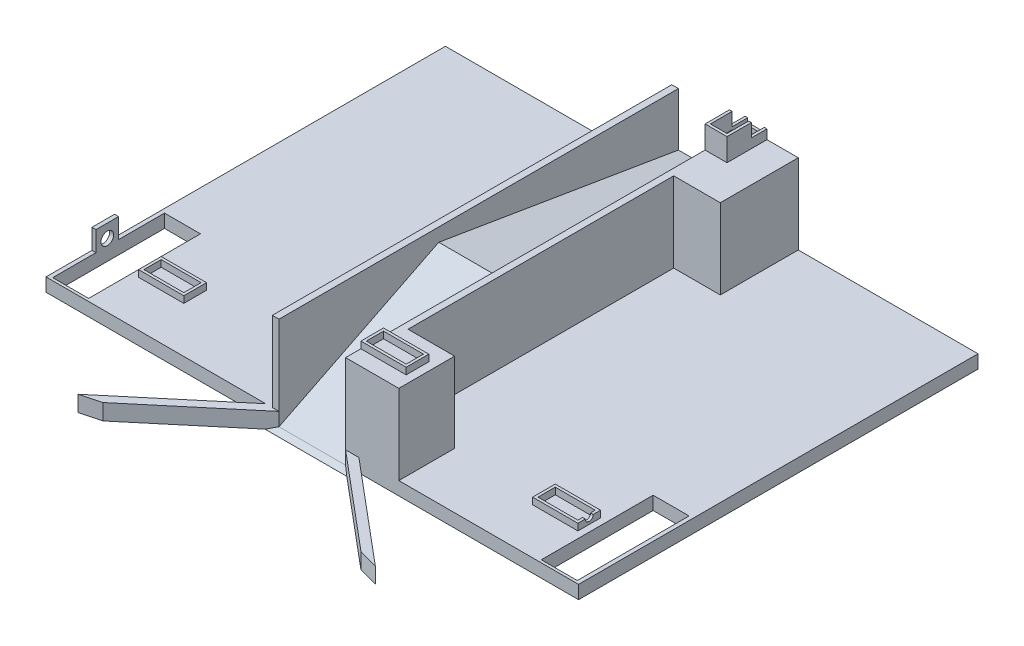
SolidWorks part; units mm, degrees
ref_plane "Front Plane" through (0, 0, 0) normal (0, 0, 1) x (1, 0, 0)
ref_plane "Top Plane" through (0, 0, 0) normal (0, 1, 0) x (1, 0, 0)
ref_plane "Right Plane" through (0, 0, 0) normal (1, 0, 0) x (0, 0, -1)
sketch "Sketch1" plane through (0, 0, 0) normal (0, 1, 0) x (1, 0, 0)
  line L1 (-117.9466, 258.1119) -> (282.0534, 258.1119)
  line L2 (-117.9466, 258.1119) -> (-117.9466, 44.1119)
  line L3 (-87.9466, -41.8881) -> (252.0534, -41.8881)
  line L5 (-117.9466, 44.1119) -> (-87.9466, 44.1119)
  line L8 (-87.9466, 44.1119) -> (-87.9466, -41.8881)
  line L23 (82.0534, 258.1119) -> (82.0534, -41.8881) construction
  line L32 (282.0534, 44.1119) -> (252.0534, 44.1119)
  line L33 (282.0534, 258.1119) -> (282.0534, 44.1119)
  line L34 (252.0534, 44.1119) -> (252.0534, -41.8881)
  point P32 (199.0884, -22.3492)
  dimension "D3" = 200
  dimension "D4" = 300
  dimension "D2" = 86
  dimension "D11" = 30
  dimension "D5" = 170
extrude "Boss-Extrude3" add sketch "Sketch1" along normal blind 10
sketch "Sketch2" plane through (0, 10, 0) normal (0, 1, 0) x (1, 0, 0)
  line L1 (-82.9466, 9.6119) -> (-48.9466, 9.6119)
  line L2 (-87.9466, 44.1119) -> (-87.9466, -41.8881) construction
  line L3 (-82.9466, 9.6119) -> (-82.9466, -7.3881)
  line L4 (-82.9466, -7.3881) -> (-48.9466, -7.3881)
  line L5 (-48.9466, 9.6119) -> (-48.9466, -7.3881)
  line L7 (-80.9466, 7.6119) -> (-50.9466, 7.6119)
  line L8 (-80.9466, 7.6119) -> (-80.9466, -5.3881)
  line L9 (-80.9466, -5.3881) -> (-50.9466, -5.3881)
  line L10 (-50.9466, 7.6119) -> (-50.9466, -5.3881)
  line L11 (-48.9466, 1.1119) -> (-82.9466, 1.1119) construction
  line L12 (-87.9466, -41.8881) -> (252.0534, -41.8881) construction
  line L13 (82.0534, 258.1119) -> (82.0534, -41.8881) construction
  line L14 (282.0534, 258.1119) -> (-117.9466, 258.1119) construction
  line L15 (213.0534, 1.1119) -> (247.0534, 1.1119) construction
  line L17 (215.0534, 7.6119) -> (215.0534, -5.3881)
  line L18 (245.0534, -5.3881) -> (215.0534, -5.3881)
  line L19 (245.0534, 7.6119) -> (245.0534, -5.3881)
  line L20 (245.0534, 7.6119) -> (215.0534, 7.6119)
  line L21 (213.0534, 9.6119) -> (213.0534, -7.3881)
  line L22 (247.0534, -7.3881) -> (213.0534, -7.3881)
  line L23 (247.0534, 9.6119) -> (247.0534, -7.3881)
  line L24 (247.0534, 9.6119) -> (213.0534, 9.6119)
  dimension "D1" = 2
  dimension "D3" = 2
  dimension "D4" = 2
  dimension "D5" = 30
  dimension "D6" = 13
  dimension "D7" = 43
  dimension "D2" = 2
  dimension "D8" = 5
extrude "Boss-Extrude4" add sketch "Sketch2" along normal blind 5
sketch "Sketch3" plane through (0, 10, 0) normal (0, 1, 0) x (1, 0, 0)
  line L0 (82.0534, 258.1119) -> (82.0534, -41.8881) construction
  line L1 (282.0534, 258.1119) -> (-117.9466, 258.1119) construction
  line L2 (-87.9466, -41.8881) -> (252.0534, -41.8881) construction
  line L3 (57.0534, -41.8881) -> (57.0534, 78.1119)
  line L4 (57.0534, 78.1119) -> (107.0534, 78.1119)
  line L5 (107.0534, 78.1119) -> (107.0534, -41.8881)
  line L24 (252.0534, -41.8881) -> (252.0534, 44.1119)
  line L25 (252.0534, 44.1119) -> (282.0534, 44.1119)
  line L26 (282.0534, 44.1119) -> (282.0534, 258.1119)
  line L27 (282.0534, 258.1119) -> (-117.9466, 258.1119)
  line L28 (-117.9466, 258.1119) -> (-117.9466, 44.1119)
  line L29 (-117.9466, 44.1119) -> (-87.9466, 44.1119)
  line L30 (-87.9466, 44.1119) -> (-87.9466, -41.8881)
  line L35 (-87.9466, -41.8881) -> (252.0534, -41.8881)
  line L51 (57.0534, -41.8881) -> (107.0534, -41.8881)
  dimension "D1" = 50
  dimension "D2" = 25
  dimension "D3" = 120
extrude "Boss-Extrude5" add sketch "Sketch3" along normal blind 50
sketch "Sketch4" plane through (107.0534, 0, 0) normal (1, 0, 0) x (0, 0, -1)
  line L2 (-41.8881, 60) -> (78.1119, 60)
  line L3 (78.1119, 60) -> (-41.8881, 0)
  line L4 (-41.8881, 60) -> (-41.8881, 0)
extrude "Cut-Extrude2" cut sketch "Sketch4" against normal up to vertex (50 mm away) up to point (57.0534, 60, 41.8881)
sketch "Sketch5" plane through (0, 10, 0) normal (0, 1, 0) x (1, 0, 0)
  line L0 (57.0534, 78.1119) -> (57.0534, 258.1119)
  line L1 (282.0534, 258.1119) -> (-117.9466, 258.1119) construction
  line L2 (57.0534, 258.1119) -> (107.0534, 258.1119)
  line L3 (107.0534, 258.1119) -> (107.0534, 78.1119)
  line L4 (57.0534, 78.1119) -> (107.0534, 78.1119)
  line L5 (57.0534, 78.1119) -> (57.0534, -21.8881) construction
extrude "Boss-Extrude6" add sketch "Sketch5" along normal blind 50
sketch "Sketch6" plane through (107.0534, 0, 0) normal (1, 0, 0) x (0, 0, -1)
  line L2 (78.1119, 60) -> (258.1119, 60)
  line L3 (258.1119, 60) -> (258.1119, 30)
  line L4 (258.1119, 60) -> (258.1119, 10) construction
  line L5 (258.1119, 30) -> (78.1119, 60)
  dimension "D1" = 30
extrude "Cut-Extrude3" cut sketch "Sketch6" against normal through all contours L2 L3 L5
sketch "Sketch7" plane through (0, 0, 0) normal (0, 1, 0) x (1, 0, 0)
  line L0 (52.0534, 258.1119) -> (52.0534, -41.8881)
  line L1 (57.0534, 258.1119) -> (-117.9466, 258.1119) construction
  line L2 (-87.9466, -41.8881) -> (57.0534, -41.8881) construction
  line L3 (52.0534, -41.8881) -> (57.0534, -41.8881)
  line L4 (57.0534, -41.8881) -> (57.0534, 258.1119)
  line L5 (57.0534, 258.1119) -> (57.0534, -21.8881) construction
  line L6 (57.0534, 258.1119) -> (107.0534, 258.1119) construction
  line L7 (57.0534, 258.1119) -> (52.0534, 258.1119)
  line L8 (107.0534, 258.1119) -> (112.0534, 258.1119)
  line L9 (282.0534, 258.1119) -> (107.0534, 258.1119) construction
  line L10 (112.0534, 258.1119) -> (112.0534, -41.8881)
  line L11 (107.0534, -41.8881) -> (252.0534, -41.8881) construction
  line L12 (112.0534, -41.8881) -> (107.0534, -41.8881)
  line L13 (107.0534, -41.8881) -> (107.0534, 258.1119)
  line L14 (112.0534, -41.8881) -> (147.0534, -41.8881)
  line L15 (107.0534, -41.8881) -> (252.0534, -41.8881) construction
  line L16 (147.0534, -41.8881) -> (147.0534, 0)
  line L17 (147.0534, 0) -> (112.0534, 0)
  dimension "D1" = 5
  dimension "D2" = 5
  dimension "D3" = 35
extrude "Boss-Extrude7" add sketch "Sketch7" along normal blind 70 contours L16 L17 L10 L14 | L7 L0 L3 L4 | L13 L8 L10 L12 region at (129.5534, 0, 20.9441)
sketch "Sketch9" plane through (0, 70, 0) normal (0, 1, 0) x (1, 0, 0)
  line L0 (107.0534, -41.8881) -> (107.0534, 78.1119) construction
  line L1 (107.0534, -13.3881) -> (141.0534, -13.3881)
  line L2 (107.0534, -13.3881) -> (107.0534, -30.3881)
  line L3 (107.0534, -30.3881) -> (141.0534, -30.3881)
  line L4 (141.0534, -13.3881) -> (141.0534, -30.3881)
  line L5 (141.0534, -21.8881) -> (107.0534, -21.8881) construction
  line L6 (109.0534, -15.3881) -> (139.0534, -15.3881)
  line L7 (109.0534, -15.3881) -> (109.0534, -28.3881)
  line L8 (109.0534, -28.3881) -> (139.0534, -28.3881)
  line L9 (139.0534, -15.3881) -> (139.0534, -28.3881)
  line L10 (124.0534, -13.3881) -> (124.0534, -35.4954) construction
  line L11 (147.0534, -41.8881) -> (107.0534, -41.8881) construction
  dimension "D1" = 2
  dimension "D2" = 2
  dimension "D3" = 2
  dimension "D4" = 2
  dimension "D5" = 30
  dimension "D6" = 13
  dimension "D7" = 20
extrude "Boss-Extrude8" add sketch "Sketch9" along normal blind 5 contours L2 L1 L4 L3 | L7 L6 L9 L8
sketch "Sketch10" plane through (112.0534, 0, 0) normal (1, 0, 0) x (0, 0, -1)
  line L0 (199.5615, 70) -> (199.5615, 10)
  line L1 (258.1119, 70) -> (0, 70) construction
  line L2 (0, 10) -> (258.1119, 10) construction
  line L3 (199.5615, 10) -> (258.1119, 10)
  line L4 (258.1119, 10) -> (258.1119, 70)
  line L5 (258.1119, 70) -> (199.5615, 70)
extrude "Boss-Extrude9" add sketch "Sketch10" along normal blind 35
sketch "Sketch13" plane through (0, 70, 0) normal (0, 1, 0) x (1, 0, 0)
  line L0 (123.5534, 228.1119) -> (107.0534, 228.1119)
  line L2 (107.0534, 228.1119) -> (107.0534, 258.1119)
  line L3 (107.0534, 258.1119) -> (123.5534, 258.1119)
  line L4 (123.5534, 258.1119) -> (123.5534, 228.1119)
  line L5 (121.5534, 230.1119) -> (109.0534, 230.1119)
  line L6 (109.0534, 230.1119) -> (109.0534, 256.1119)
  line L7 (109.0534, 256.1119) -> (121.5534, 256.1119)
  line L8 (121.5534, 256.1119) -> (121.5534, 230.1119)
  line L15 (107.0534, 258.1119) -> (147.0534, 258.1119) construction
  dimension "D2" = 16.5
  dimension "D3" = 30
  dimension "D4" = 2
  dimension "D5" = 2
  dimension "D6" = 2
  dimension "D7" = 2
extrude "Boss-Extrude11" add sketch "Sketch13" along normal blind 7
sketch "Sketch14" plane through (0, 0, 0) normal (0, -1, 0) x (1, 0, 0)
  line L0 (282.0534, -44.1119) -> (282.0534, -258.1119) construction
  line L1 (282.0534, -258.1119) -> (-117.9466, -258.1119) construction
  circle A0 centre (267.0534, -243.1119) radius 8
  dimension "D1" = 15
  dimension "D2" = 15
sketch "Sketch16" plane through (0, 0, 0) normal (0, -1, 0) x (1, 0, 0)
  line L0 (-117.9466, -258.1119) -> (-117.9466, -44.1119) construction
  line L1 (282.0534, -258.1119) -> (-117.9466, -258.1119) construction
  circle A0 centre (-102.9466, -243.1119) radius 8
  dimension "D1" = 15
  dimension "D2" = 15
sketch "Sketch19" plane through (0, 0, 41.8881) normal (0, 0, 1) x (1, 0, 0)
  line L0 (-87.9466, 10) -> (52.0534, 10) construction
  line L1 (57.0534, 0) -> (47.0534, 0)
  line L2 (57.0534, 0) -> (57.0534, 10)
  line L3 (57.0534, 10) -> (47.0534, 10)
  line L4 (47.0534, 0) -> (47.0534, 10)
  line L6 (107.0534, 0) -> (117.0534, 0)
  line L7 (107.0534, 0) -> (107.0534, 10)
  line L8 (107.0534, 10) -> (117.0534, 10)
  line L9 (117.0534, 0) -> (117.0534, 10)
  dimension "D1" = 10
  dimension "D2" = 10
  dimension "D3" = 10
sketch "Sketch20" plane through (0, 0, 0) normal (0, 1, 0) x (1, 0, 0)
  line L0 (47.0534, -41.8881) -> (-29.551, -106.1669)
  line L2 (57.0534, -41.8881) -> (-14.8596, -102.2304)
  line L4 (-87.9466, -41.8881) -> (52.0534, -41.8881) construction
  line L5 (107.0534, -41.8881) -> (178.9665, -102.2304)
  line L6 (117.0534, -41.8881) -> (193.6579, -106.1669)
  line L7 (107.0534, -41.8881) -> (117.0534, -41.8881) construction
  line L8 (147.0534, -41.8881) -> (107.0534, -41.8881) construction
  line L9 (178.9665, -102.2304) -> (193.6579, -106.1669)
  line L10 (-14.8596, -102.2304) -> (-29.551, -106.1669)
  line L11 (47.0534, -41.8881) -> (57.0534, -41.8881)
  line L12 (107.0534, -41.8881) -> (117.0534, -41.8881)
  dimension "D1" = 40
  dimension "D2" = 40
  dimension "D3" = 25
  dimension "D4" = 25
  dimension "D5" = 100
  dimension "D6" = 100
  dimension "D7" = 10
  dimension "D8" = 10
extrude "Boss-Extrude16" add sketch "Sketch20" along normal blind 10 and the other way blind 2
sketch "Sketch21" plane through (0, 0, 0) normal (0, -1, 0) x (1, 0, 0)
  line L1 (57.0534, 41.8881) -> (107.0534, 41.8881)
  line L2 (57.0534, 31.8881) -> (57.0534, 11.8881)
  line L3 (57.0534, 11.8881) -> (107.0534, 11.8881)
  line L4 (107.0534, 31.8881) -> (107.0534, 11.8881)
  line L5 (47.0534, 41.8881) -> (47.0534, 31.8881)
  line L6 (47.0534, 31.8881) -> (57.0534, 31.8881)
  line L7 (117.0534, 41.8881) -> (117.0534, 31.8881)
  line L8 (107.0534, 41.8881) -> (117.0534, 41.8881) construction
  line L9 (117.0534, 31.8881) -> (107.0534, 31.8881)
  line L10 (47.0534, 41.8881) -> (57.0534, 41.8881)
  line L11 (107.0534, 41.8881) -> (117.0534, 41.8881)
  dimension "D1" = 50
  dimension "D2" = 30
  dimension "D3" = 10
  dimension "D4" = 10
extrude "Boss-Extrude19" add sketch "Sketch21" along normal blind 2
sketch "Sketch23" plane through (107.0534, 0, 0) normal (1, 0, 0) x (0, 0, -1)
  line L4 (-41.8881, 0) -> (-46.6881, -2)
  line L5 (-102.2304, -2) -> (-41.8881, -2) construction
  line L6 (-46.6881, -2) -> (-41.8881, -2)
  line L7 (-41.8881, -2) -> (-41.8881, 0) construction
  line L8 (-41.8881, 0) -> (-41.8881, -2)
  dimension "D1" = 22.62
extrude "Boss-Extrude23" add sketch "Sketch23" against normal up to surface and the other way up to surface separate body contours L8 L6 L4 up to face at (28.2882, 3.2, 66.025) other way up to face at (135.8187, 3.2, 66.025)
sketch "Sketch28" plane through (0, 0, -44.1119) normal (0, 0, 1) x (1, 0, 0)
  line L0 (-117.9466, 0) -> (-87.9466, 0) construction
  line L1 (-117.9466, 10) -> (-114.9466, 10)
  line L2 (-117.9466, 10) -> (-117.9466, 0)
  line L3 (-117.9466, 0) -> (-114.9466, 0)
  line L4 (-114.9466, 10) -> (-114.9466, 0)
  dimension "D1" = 3
extrude "Boss-Extrude24" add sketch "Sketch28" along normal up to vertex (86 mm away) up to point (-87.9466, 0, 41.8881)
sketch "Sketch30" plane through (0, 0, -44.1119) normal (0, 0, 1) x (1, 0, 0)
  line L0 (252.0534, 0) -> (282.0534, 0) construction
  line L1 (282.0534, 10) -> (279.0534, 10)
  line L2 (282.0534, 10) -> (282.0534, 0)
  line L3 (282.0534, 0) -> (279.0534, 0)
  line L4 (279.0534, 10) -> (279.0534, 0)
  dimension "D1" = 3
extrude "Boss-Extrude26" add sketch "Sketch30" along normal up to vertex (86 mm away) up to point (252.0534, 0, 41.8881)
sketch "Sketch32" plane through (0, 70, 0) normal (0, 1, 0) x (1, 0, 0)
  line L0 (109.0534, 256.1119) -> (109.0534, 230.1119) construction
  line L1 (121.5534, 230.1119) -> (109.0534, 230.1119)
  line L2 (121.5534, 230.1119) -> (121.5534, 246.4119)
  line L3 (121.5534, 246.4119) -> (109.0534, 246.4119)
  line L4 (109.0534, 230.1119) -> (109.0534, 246.4119)
  dimension "D1" = 16.3
extrude "Boss-Extrude28" add sketch "Sketch32" along normal blind 5
sketch "Sketch34" plane through (0, 77, 0) normal (0, 1, 0) x (1, 0, 0)
  line L0 (109.0534, 246.4119) -> (107.0534, 246.4119)
  line L1 (107.0534, 258.1119) -> (107.0534, 228.1119) construction
  line L2 (107.0534, 246.4119) -> (107.0534, 228.1119)
  line L3 (107.0534, 228.1119) -> (123.5534, 228.1119)
  line L4 (107.0534, 228.1119) -> (123.5534, 228.1119) construction
  line L5 (123.5534, 228.1119) -> (123.5534, 246.4119)
  line L6 (123.5534, 228.1119) -> (123.5534, 258.1119) construction
  line L7 (123.5534, 246.4119) -> (121.5534, 246.4119)
  line L8 (121.5534, 246.4119) -> (121.5534, 230.1119)
  line L9 (121.5534, 230.1119) -> (109.0534, 230.1119)
  line L10 (109.0534, 230.1119) -> (109.0534, 246.4119)
extrude "Boss-Extrude31" add sketch "Sketch34" along normal blind 10
sketch "Sketch35" plane through (0, 0, -258.1119) normal (0, 0, -1) x (-1, 0, 0)
  line L0 (-121.5534, 77) -> (-121.5534, 74)
  line L1 (-123.5534, 77) -> (-107.0534, 77) construction
  line L2 (-121.5534, 74) -> (-109.0534, 74)
  line L3 (-109.0534, 74) -> (-109.0534, 77)
  line L4 (-123.5534, 77) -> (-123.5534, 70) construction
  line L5 (-107.0534, 77) -> (-107.0534, 30) construction
  line L6 (-121.5534, 77) -> (-109.0534, 77)
  dimension "D1" = 2
  dimension "D2" = 2
  dimension "D3" = 3
extrude "Cut-Extrude4" cut sketch "Sketch35" against normal up to next (2 mm away)
sketch "Sketch47" plane through (247.0534, 0, 0) normal (1, 0, 0) x (0, 0, -1)
  line L0 (-7.3881, 15) -> (9.6119, 15) construction
  line L1 (-1.8881, 15) -> (4.1119, 15)
  arc A0 (4.1119, 15) -> (-1.8881, 15) centre (1.1119, 15) cw
  dimension "D1" = 3
extrude "Cut-Extrude14" cut sketch "Sketch47" against normal up to next (2 mm away)
sketch "Sketch41" plane through (0, 10, 0) normal (0, 1, 0) x (1, 0, 0)
  line L0 (-117.9466, 9.6119) -> (-114.9466, 9.6119)
  line L1 (-117.9466, -41.8881) -> (-117.9466, 258.1119) construction
  line L2 (-114.9466, -41.8881) -> (-114.9466, 44.1119) construction
  line L3 (-114.9466, 9.6119) -> (-114.9466, -7.3881)
  line L4 (-114.9466, -7.3881) -> (-117.9466, -7.3881)
  line L5 (-117.9466, -7.3881) -> (-117.9466, 9.6119)
  line L6 (-117.9466, 9.6119) -> (-82.9466, 9.6119) construction
  line L7 (-117.9466, -7.3881) -> (-82.9466, -7.3881) construction
extrude "Boss-Extrude33" add sketch "Sketch41" along normal blind 15
sketch "Sketch42" plane through (-117.9466, 0, 0) normal (-1, 0, 0) x (0, 0, 1)
  line L0 (-9.6119, 25) -> (-9.6119, 10) construction
  line L3 (-9.6119, 15) -> (7.3881, 15) construction
  line L4 (7.3881, 25) -> (7.3881, 10) construction
  line L5 (41.8881, 10) -> (-258.1119, 10) construction
  circle A0 centre (-1.1119, 15) radius 4.75
  dimension "D2" = 9.5
  dimension "D1" = 5
extrude "Cut-Extrude11" cut sketch "Sketch42" against normal up to next (3 mm away)
extrude "Boss-Extrude34" add sketch "Sketch14" along normal blind 5
extrude "Boss-Extrude35" add sketch "Sketch16" along normal blind 5
sketch "Sketch43" plane through (-87.9466, 0, 0) normal (-1, 0, 0) x (0, 0, 1)
  line L0 (-44.1119, 0) -> (41.8881, 0) construction
  line L1 (41.8881, 10) -> (39.8881, 10)
  line L2 (41.8881, 10) -> (41.8881, 0)
  line L3 (41.8881, 0) -> (39.8881, 0)
  line L4 (39.8881, 10) -> (39.8881, 0)
  dimension "D1" = 2
extrude "Boss-Extrude36" add sketch "Sketch43" along normal up to next (27 mm away)
sketch "Sketch44" plane through (252.0534, 0, 0) normal (1, 0, 0) x (0, 0, -1)
  line L0 (-41.8881, 0) -> (44.1119, 0) construction
  line L1 (-41.8881, 10) -> (-39.8881, 10)
  line L2 (-41.8881, 10) -> (-41.8881, 0)
  line L3 (-41.8881, 0) -> (-39.8881, 0)
  line L4 (-39.8881, 10) -> (-39.8881, 0)
  dimension "D1" = 2
extrude "Boss-Extrude37" add sketch "Sketch44" along normal up to next
equation "\"draggingScrewDiameter\"= 2"
equation "\"chassisWidth\"= 400"
equation "\"D3@Sketch1\"=0.5 * \"chassisWidth\""
equation "\"chassisLength\"=300"
equation "\"D4@Sketch1\"=\"chassisLength\""
equation "\"wheelDepth\"= 86"
equation "\"D2@Sketch1\"=\"wheelDepth\""
equation "\"wheelWidth\"= 30"
equation "\"baseThickness\"=10"
equation "\"D1@Boss-Extrude3\"=\"baseThickness\""
equation "\"D7@Sketch2\"=\"wheelDepth\" * 0.5"
equation "\"rampLength\"=120"
equation "\"D3@Sketch3\"=\"rampLength\""
equation "\"rampHeight\"=50"
equation "\"D1@Boss-Extrude5\"=\"rampHeight\""
equation "\"D1@Boss-Extrude6\"=\"rampHeight\""
equation "\"dumpHeight\"=30"
equation "\"D1@Sketch6\"=\"dumpHeight\""
equation "\"D11@Sketch1\"=\"wheelWidth\""
equation "\"D5@Sketch1\"=(0.5 * \"chassisWidth\") - \"wheelWidth\""
equation "\"D1@Sketch23\"=atn(\"rampHeight\"/\"rampLength\")"
